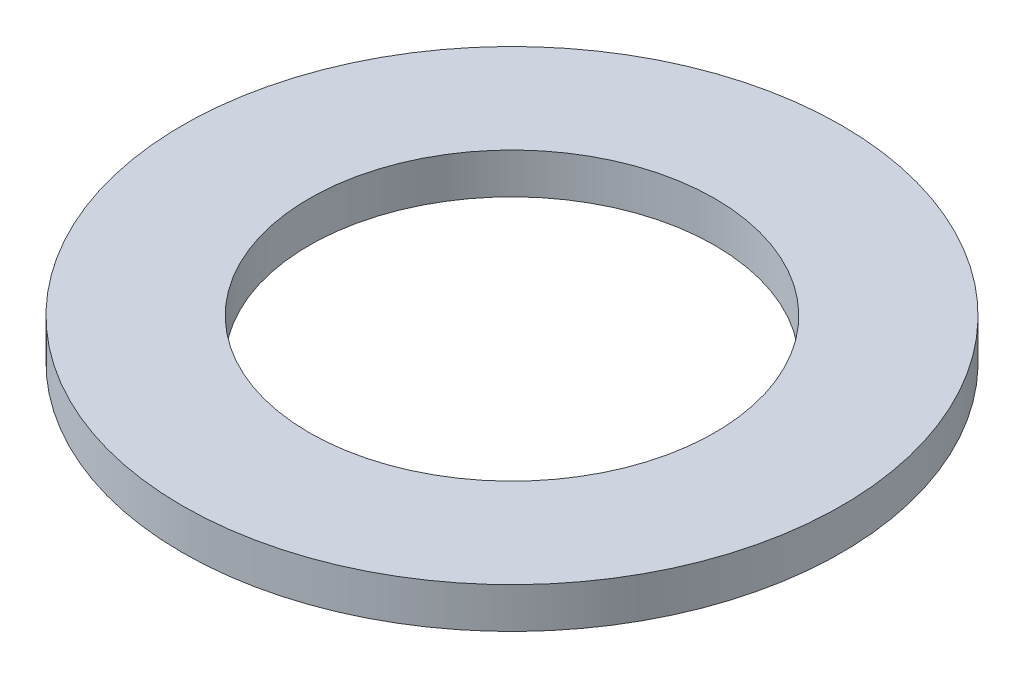
SolidWorks part; units mm, degrees
ref_plane "Front Plane" through (0, 0, 0) normal (0, 0, 1) x (1, 0, 0)
ref_plane "Top Plane" through (0, 0, 0) normal (0, 1, 0) x (1, 0, 0)
ref_plane "Right Plane" through (0, 0, 0) normal (1, 0, 0) x (0, 0, -1)
sketch "Sketch1" plane through (0, 0, 0) normal (0, 1, 0) x (1, 0, 0)
  circle A0 centre (0, 0) radius 32.5
  dimension "FLANGE_OD" = 65
extrude "Boss-Extrude1" add sketch "Sketch1" along normal blind 4
sketch "Sketch2" plane through (0, 0, 0) normal (0, 1, 0) x (1, 0, 0)
  circle A0 centre (0, 0) radius 20
  dimension "BORE_D" = 40
extrude "Cut-Extrude1" cut sketch "Sketch2" along normal through all
sketch "Sketch3" plane through (0, 4, 0) normal (0, 1, 0) x (1, 0, 0)
  circle A0 centre (0, 0) radius 12.9449 construction
  circle A1 centre (-12.9449, 0) radius 1.509
  dimension "BOLT_D" = 3.018
  dimension "BOLT_PCD" = 25.8898
extrude "Cut-Extrude2" cut sketch "Sketch3" against normal blind 3.4708 rebuild error yes
pattern_circular "CirPattern1" count 8 over 360 rebuild error yes
